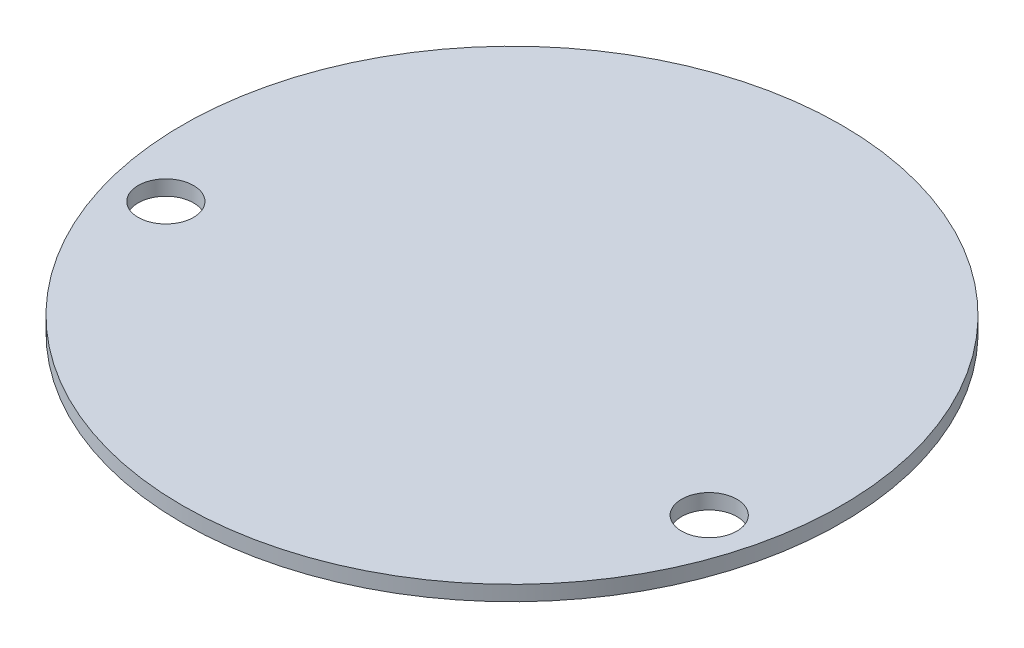
SolidWorks part; units mm, degrees
material "ABS"
ref_plane "Front Plane" through (0, 0, 0) normal (0, 0, 1) x (1, 0, 0)
ref_plane "Top Plane" through (0, 0, 0) normal (0, 1, 0) x (1, 0, 0)
ref_plane "Right Plane" through (0, 0, 0) normal (1, 0, 0) x (0, 0, -1)
sketch "Sketch1" plane through (0, 0, 0) normal (0, 1, 0) x (1, 0, 0)
  line L0 (-27, -7.4) -> (27, -7.4) construction
  circle A0 centre (0, 0) radius 32.75
  circle A1 centre (-27, -7.4) radius 2.75
  circle A2 centre (27, -7.4) radius 2.75
  point P7 (0, -7.4)
  dimension "D2" = 5.5
  dimension "D3" = 65.5
  dimension "D1" = 54
  dimension "D4" = 7.4
extrude "Boss-Extrude1" add sketch "Sketch1" along normal blind 1.5
